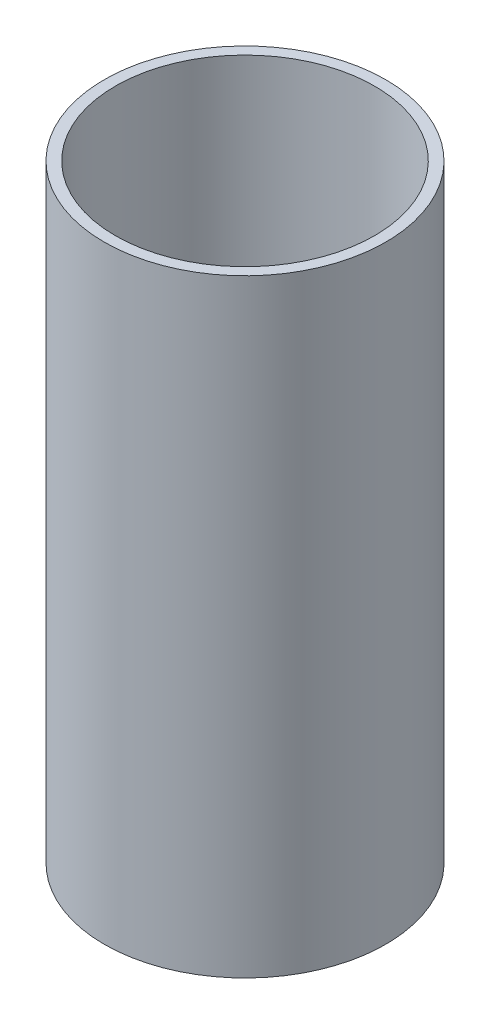
SolidWorks part; units mm, degrees
ref_plane "Front Plane" through (0, 0, 0) normal (0, 0, 1) x (1, 0, 0)
ref_plane "Top Plane" through (0, 0, 0) normal (0, 1, 0) x (1, 0, 0)
ref_plane "Right Plane" through (0, 0, 0) normal (1, 0, 0) x (0, 0, -1)
sketch "Sketch1" plane through (0, 0, 0) normal (0, 1, 0) x (1, 0, 0)
  circle A0 centre (0, 0) radius 19
  circle A1 centre (0, 0) radius 17.5
  dimension "D1" = 1.5
  dimension "D2" = 38
extrude "Boss-Extrude1" add sketch "Sketch1" along normal blind 80.1
extrude "Ressalto-extrusão1" add sketch "Sketch1<2>" against normal blind 2 contours A0
sketch "Sketch1<2>" plane through (0, 0, 0) normal (0, 1, 0) x (1, 0, 0) same geometry as "Sketch1"
